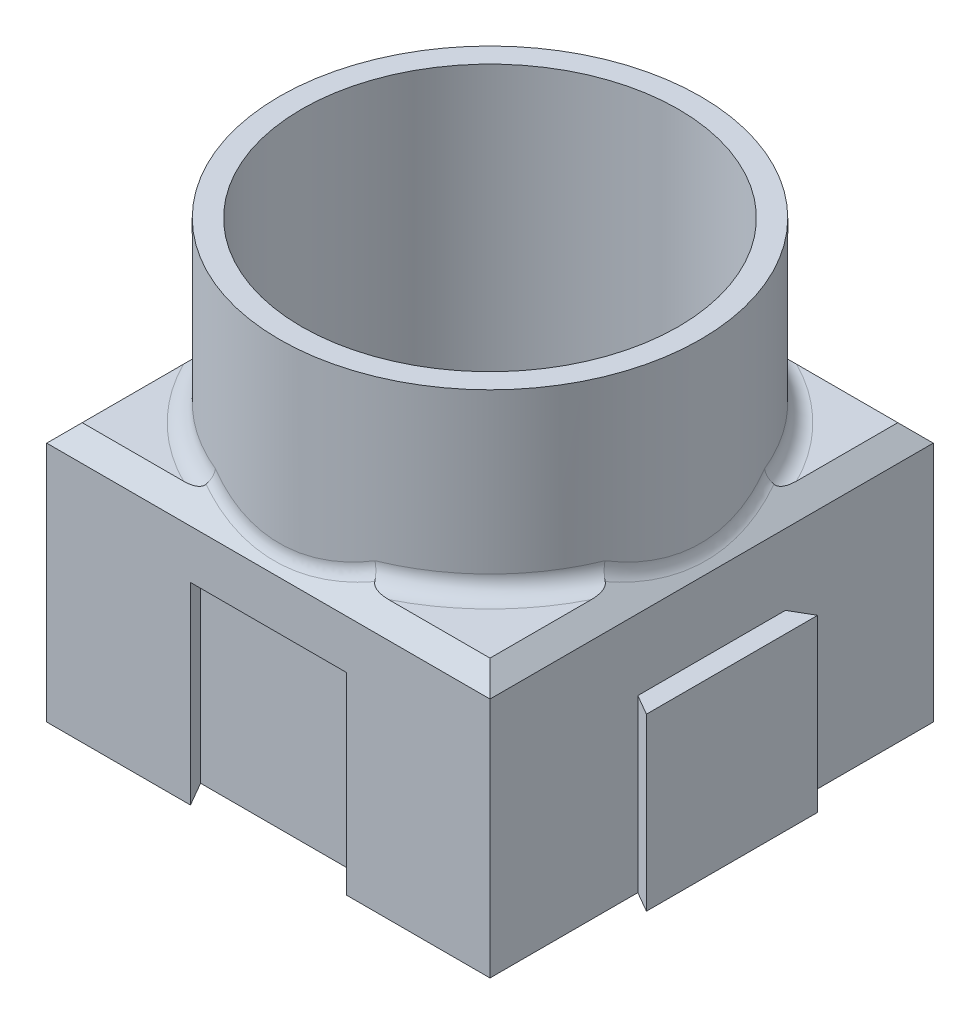
SolidWorks part; units mm, degrees
ref_plane "Front Plane" through (0, 0, 0) normal (0, 0, 1) x (1, 0, 0)
ref_plane "Top Plane" through (0, 0, 0) normal (0, 1, 0) x (1, 0, 0)
ref_plane "Right Plane" through (0, 0, 0) normal (1, 0, 0) x (0, 0, -1)
sketch "Sketch1" plane through (0, 0, 0) normal (0, 1, 0) x (1, 0, 0)
  line L1 (0, 0) -> (50, 0)
  line L2 (0, 0) -> (0, 50)
  line L3 (0, 50) -> (50, 50)
  line L4 (50, 0) -> (50, 50)
  dimension "D1" = 50
extrude "Boss-Extrude1" add sketch "Sketch1" along normal blind 30
sketch "Sketch2" plane through (0, 30, 0) normal (0, 1, 0) x (1, 0, 0)
  line L0 (0, 0) -> (50, 50) construction
  line L1 (0, 50) -> (50, 0) construction
  line L2 (25, 25) -> (3.75, 25) construction
  line L3 (3.75, 25) -> (1.25, 25) construction
  circle A0 centre (25, 25) radius 21.25
  circle A1 centre (25, 25) radius 23.75
  dimension "D1" = 42.5
  dimension "D2" = 2.5
extrude "Cut-Extrude1" cut sketch "Sketch2" against normal blind 26 contours A0
sketch "Sketch3" plane through (0, 0, 0) normal (0, 1, 0) x (1, 0, 0)
  line L0 (50, 33.5566) -> (52.5, 35) construction
  line L1 (50, 0) -> (50, 50) construction
  line L2 (52.5, 35) -> (52.5, 15) construction
  line L3 (52.5, 15) -> (50, 16.4434) construction
  line L4 (50, 25) -> (52.5, 25) construction
  line L5 (16.4434, 50) -> (15, 52.5) construction
  line L6 (50, 50) -> (0, 50) construction
  line L7 (15, 52.5) -> (35, 52.5) construction
  line L8 (35, 52.5) -> (33.5566, 50) construction
  line L9 (25, 52.5) -> (25, 50) construction
  line L10 (0, 33.5566) -> (2.5, 35) construction
  line L11 (0, 50) -> (0, 0) construction
  line L12 (2.5, 35) -> (2.5, 15) construction
  line L13 (2.5, 15) -> (0, 16.4434) construction
  line L14 (0, 25) -> (2.5, 25) construction
  line L15 (16.4434, 0) -> (15, 2.5) construction
  line L16 (0, 0) -> (50, 0) construction
  line L17 (15, 2.5) -> (35, 2.5) construction
  line L18 (35, 2.5) -> (33.5566, 0) construction
  line L19 (25, 0) -> (25, 2.5) construction
  line L20 (50, 16.6743) -> (50, 33.3257)
  line L21 (33.3257, 50) -> (16.6743, 50)
  line L23 (16.4434, 0) -> (33.5566, 0) construction
  line L24 (50, 33.3257) -> (52.3, 34.6536)
  line L25 (52.3, 34.6536) -> (52.3, 15.3464)
  line L26 (52.3, 15.3464) -> (50, 16.6743)
  line L27 (52.3, 34.6536) -> (52.2, 34.8268) construction
  line L28 (16.2124, 0) -> (14.6536, 2.7)
  line L29 (52.3, 34.6536) -> (52.5, 34.6536) construction
  line L30 (14.6536, 2.7) -> (35.3464, 2.7)
  line L31 (35.3464, 2.7) -> (33.7876, 0)
  line L32 (33.7876, 0) -> (16.2124, 0)
  line L33 (35, 2.5) -> (35, 2.7) construction
  line L34 (35, 2.5) -> (35.1732, 2.4) construction
  line L35 (0, 33.7876) -> (2.7, 35.3464)
  line L36 (2.7, 35.3464) -> (2.7, 14.6536)
  line L37 (2.7, 14.6536) -> (0, 16.2124)
  line L38 (0, 16.2124) -> (0, 33.7876)
  line L39 (2.4, 14.8268) -> (2.5, 15) construction
  line L40 (2.5, 15) -> (2.7, 15) construction
  line L41 (16.6743, 50) -> (15.3464, 52.3)
  line L42 (15.3464, 52.3) -> (34.6536, 52.3)
  line L43 (34.6536, 52.3) -> (33.3257, 50)
  line L44 (15.3464, 52.5) -> (15.3464, 52.3) construction
  line L45 (15.1732, 52.2) -> (15.3464, 52.3) construction
  point P8 (50, 25)
  point P39 (52.3, 25)
  point P40 (25, 0)
  point P53 (0, 25)
  point P59 (25, 52.3)
  point P63 (25, 50)
  dimension "D1" = 0.2
  dimension "D2" = 60
  dimension "D3" = 2.5
  dimension "D4" = 20
extrude "Boss-Extrude2" add sketch "Sketch3" along normal blind 20 contours L20 L24 L25 L26
extrude "Boss-Extrude3" add sketch "Sketch3<3>" along normal blind 20 contours L21 L41 L42 L43
sketch "Sketch3<3>" plane through (0, 0, 0) normal (0, 1, 0) x (1, 0, 0) same geometry as "Sketch3"
extrude "Cut-Extrude5" cut sketch "Sketch3<6>" along normal blind 20 contours L38 L35 L36 L37
sketch "Sketch3<6>" plane through (0, 0, 0) normal (0, 1, 0) x (1, 0, 0) same geometry as "Sketch3"
extrude "Cut-Extrude6" cut sketch "Sketch3<7>" along normal blind 20 contours L32 L28 L30 L31
sketch "Sketch3<7>" plane through (0, 0, 0) normal (0, 1, 0) x (1, 0, 0) same geometry as "Sketch3"
extrude "Boss-Extrude4" add sketch "Sketch2<3>" along normal blind 20
sketch "Sketch2<3>" plane through (0, 30, 0) normal (0, 1, 0) x (1, 0, 0) same geometry as "Sketch2"
chamfer "Chamfer1" distance 2 angle 45 4 edges at (25, 30, -50) (50, 30, -25) (25, 30, 0) (0, 30, -25)
sketch "Sketch4" plane through (0, 0, 0) normal (0, 1, 0) x (1, 0, 0)
  line L0 (12.5, 12.5) -> (37.5, 37.5) construction
  line L1 (12.5, 12.5) -> (37.5, 12.5) construction
  line L2 (12.5, 12.5) -> (12.5, 37.5) construction
  line L3 (12.5, 37.5) -> (37.5, 37.5) construction
  line L4 (37.5, 12.5) -> (37.5, 37.5) construction
  line L5 (12.5, 37.5) -> (37.5, 12.5) construction
  line L6 (0, 0) -> (12.5, 12.5) construction
  line L7 (12.5, 37.5) -> (0, 50) construction
  line L8 (50, 50) -> (37.5, 37.5) construction
  line L9 (50, 0) -> (37.5, 12.5) construction
  line L10 (0, 25) -> (25, 25) construction
  circle A0 centre (12.5, 37.5) radius 3.1
  circle A1 centre (37.5, 37.5) radius 3.1
  circle A2 centre (37.5, 12.5) radius 3.1
  circle A3 centre (12.5, 12.5) radius 3.1
  point P15 (12.5, 25)
  dimension "D1" = 6.2
extrude "Cut-Extrude4" cut sketch "Sketch4" along normal blind 4
chamfer "Chamfer3" distance 0.75 angle 45 24 edges at (41.8938, 0, 0) (50, 0, -8.3372) (50, 0, -41.6628) (41.6628, 0, -50) (8.3372, 0, -50) (0, 0, -41.8938) (0, 0, -8.1062) (8.1062, 0, 0) (12.5, 0, -34.4) (37.5, 0, -34.4) (37.5, 0, -9.4) (12.5, 0, -9.4) (51.15, 0, -16.0104) (52.3, 0, -25) (51.15, 0, -33.9896) (33.9896, 0, -51.15) (25, 0, -52.3) (16.0104, 0, -51.15) (1.35, 0, -34.567) (2.7, 0, -25) (1.35, 0, -15.433) (15.433, 0, -1.35) (25, 0, -2.7) (34.567, 0, -1.35)
chamfer "Chamfer4" distance 2.5 angle 45 2 edges at (25, 20, 0) (0, 20, -25)
fillet "Fillet1" radius 2 8 edges at (1.25, 29.25, -25) (8.2062, 30, -41.7938) (25, 29.25, -48.75) (41.7938, 30, -41.7938) (48.75, 29.25, -25) (41.7938, 30, -8.2062) (25, 29.25, -1.25) (8.2062, 30, -8.2062)
